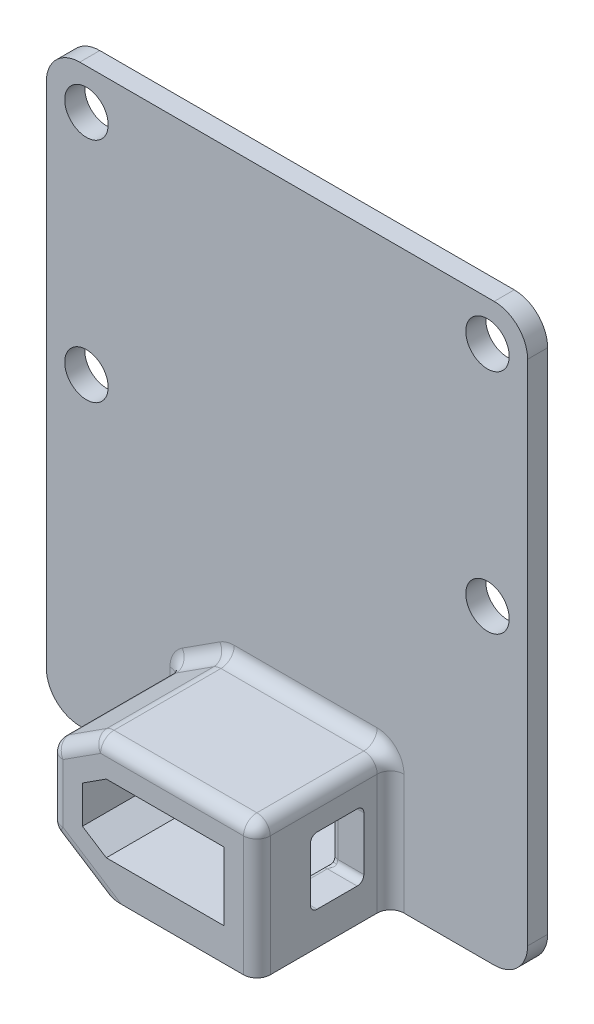
SolidWorks part; units mm, degrees
ref_plane "Plan de face" through (0, 0, 0) normal (0, 0, 1) x (1, 0, 0)
ref_plane "Plan de dessus" through (0, 0, 0) normal (0, 1, 0) x (1, 0, 0)
ref_plane "Plan de droite" through (0, 0, 0) normal (1, 0, 0) x (0, 0, -1)
sketch "Esquisse2" plane through (0, 0, 0) normal (0, 0, 1) x (1, 0, 0)
  line L0 (0, -86) -> (72, -86)
  line L1 (72, 0) -> (0, 0)
  line L4 (0, 0) -> (0, -86)
  line L10 (72, -86) -> (72, 0)
  circle A0 centre (66, -6) radius 3.25
  circle A1 centre (66, -40) radius 3.25
  circle A2 centre (6, -40) radius 3.25
  circle A3 centre (6, -6) radius 3.25
  dimension "D4" = 6.5
  dimension "D3" = 86
  dimension "D5" = 34
  dimension "D7" = 72
  dimension "D8" = 6
  dimension "D9" = 6
  dimension "D10" = 60
extrude "Boss.-Extru.1" add sketch "Esquisse2" along normal blind 3
fillet "Congé1" radius 5 4 edges at (0, 0, 1.5) (0, -86, 1.5) (72, -86, 1.5) (72, 0, 1.5)
sketch "Esquisse3" plane through (0, 0, 3) normal (0, 0, 1) x (1, 0, 0)
  line L0 (29, -71) -> (46.5, -71) construction
  line L1 (46.5, -71) -> (46.5, -81) construction
  line L2 (46.5, -81) -> (29, -81) construction
  line L3 (29, -81) -> (25.5, -78.75) construction
  line L4 (25.5, -78.75) -> (25.5, -73.25) construction
  line L5 (25.5, -73.25) -> (29, -71) construction
  line L6 (25.5, -76) -> (46.5, -76) construction
  line L7 (5, -86) -> (67, -86) construction
  line L8 (28.9706, -70.9) -> (46.6, -70.9)
  line L9 (46.6, -70.9) -> (46.6, -81.1)
  line L10 (46.6, -81.1) -> (28.9706, -81.1)
  line L11 (28.9706, -81.1) -> (25.4, -78.8046)
  line L12 (25.4, -78.8046) -> (25.4, -73.1954)
  line L13 (25.4, -73.1954) -> (28.9706, -70.9)
  point P8 (0, 0)
  point P9 (36, -76)
  point P12 (36, -86)
  dimension "D1" = 21
  dimension "D2" = 10
  dimension "D3" = 5.5
  dimension "D4" = 17.5
  dimension "D5" = 5
  dimension "D6" = 0.1
extrude "Enlèv. mat.-Extru.1" cut sketch "Esquisse3" against normal through all
sketch "Esquisse4" plane through (0, 0, 3) normal (0, 0, 1) x (1, 0, 0)
  line L18 (25.4, -73.1954) -> (25.4, -78.8046) construction
  line L19 (25.4, -78.8046) -> (28.9706, -81.1) construction
  line L20 (28.9706, -81.1) -> (46.6, -81.1) construction
  line L21 (46.6, -81.1) -> (46.6, -70.9) construction
  line L22 (46.6, -70.9) -> (28.9706, -70.9) construction
  line L23 (28.9706, -70.9) -> (25.4, -73.1954) construction
  line L24 (25.4, -73.1954) -> (25.4, -78.8046)
  line L25 (25.4, -78.8046) -> (28.9706, -81.1)
  line L26 (28.9706, -81.1) -> (46.6, -81.1)
  line L27 (46.6, -81.1) -> (46.6, -70.9)
  line L28 (46.6, -70.9) -> (28.9706, -70.9)
  line L29 (28.9706, -70.9) -> (25.4, -73.1954)
  line L30 (27.5315, -66) -> (20.5, -70.5202)
  line L31 (20.5, -70.5202) -> (20.5, -81.4798)
  line L32 (20.5, -81.4798) -> (27.5315, -86)
  line L33 (27.5315, -86) -> (51.5, -86)
  line L34 (51.5, -86) -> (51.5, -66)
  line L35 (51.5, -66) -> (27.5315, -66)
  dimension "D1" = 4.9
extrude "Boss.-Extru.2" add sketch "Esquisse4" along normal blind 20
sketch "Esquisse5" plane through (51.5, 0, 0) normal (1, 0, 0) x (0, 0, -1)
  line L0 (-23, -76) -> (-15, -76) construction
  line L2 (-23, -86) -> (-23, -66) construction
  line L3 (-15, -71) -> (-7, -71)
  line L4 (-15, -71) -> (-15, -81)
  line L5 (-15, -81) -> (-7, -81)
  line L6 (-7, -71) -> (-7, -81)
  point P2 (0, 0)
  point P8 (-7, -76)
  point P9 (-4.0549, -69.2624)
  dimension "D1" = 8
  dimension "D2" = 8
  dimension "D3" = 10
extrude "Enlèv. mat.-Extru.2" cut sketch "Esquisse5" against normal up to next
fillet "Congé2" radius 2 14 edges at (24.0157, -83.7399, 3) (20.5, -76, 3) (24.0157, -68.2601, 3) (39.5157, -66, 3) (24.0157, -83.7399, 23) (24.0157, -68.2601, 23) (20.5, -76, 23) (20.5, -81.4798, 13) (20.5, -70.5202, 13) (27.5315, -66, 13) (51.5, -76, 3) (51.5, -66, 13) (51.5, -76, 23) (39.5157, -66, 23)
fillet "Congé3" radius 1 4 edges at (49.05, -81, 7) (49.05, -71, 15) (49.05, -81, 15) (49.05, -71, 7)
fillet "Congé4" radius 1 6 edges at (46.6, -71.2929, 7.2929) (46.6, -71.2929, 14.7071) (46.6, -76, 15) (46.6, -80.7071, 14.7071) (46.6, -80.7071, 7.2929) (46.6, -76, 7)
